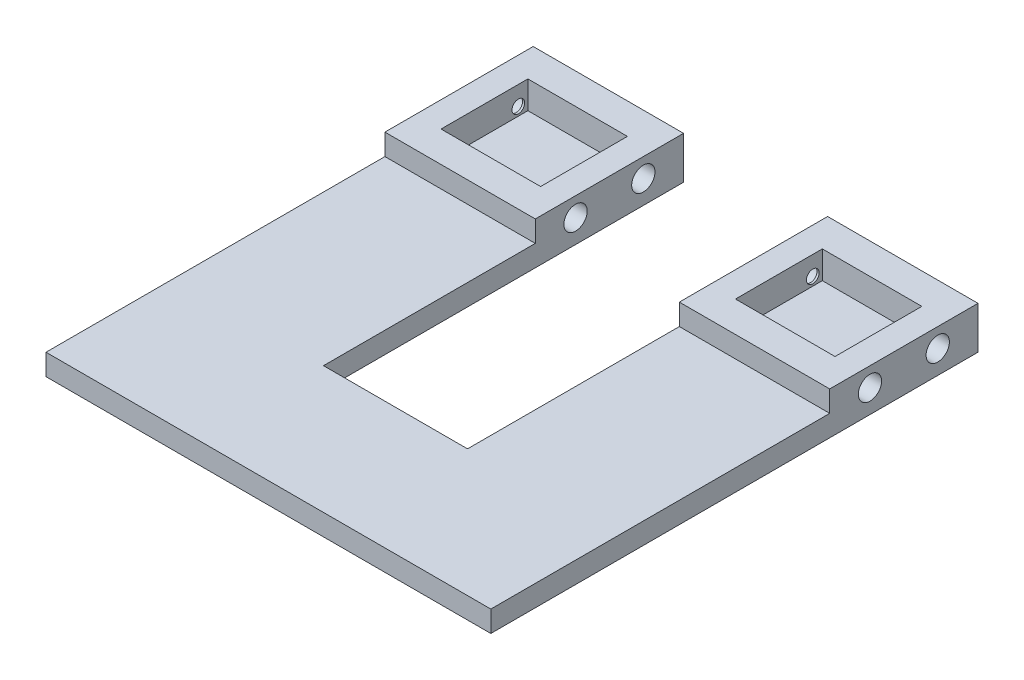
SolidWorks part; units mm, degrees
ref_plane "Front Plane" through (0, 0, 0) normal (0, 0, 1) x (1, 0, 0)
ref_plane "Top Plane" through (0, 0, 0) normal (0, 1, 0) x (1, 0, 0)
ref_plane "Right Plane" through (0, 0, 0) normal (1, 0, 0) x (0, 0, -1)
sketch "Sketch1" plane through (0, 0, 0) normal (0, 1, 0) x (1, 0, 0)
  line L1 (-11.75, 10.25) -> (11.75, 10.25)
  line L2 (-11.75, 10.25) -> (-11.75, -10.25)
  line L3 (-11.75, -10.25) -> (11.75, -10.25)
  line L4 (11.75, 10.25) -> (11.75, -10.25)
  line L5 (0, -10.25) -> (0, 10.25) construction
  line L6 (-11.75, 0) -> (11.75, 0) construction
  line L7 (-17.75, -17.5) -> (17.75, -17.5)
  line L8 (-17.75, -17.5) -> (-17.75, 17.5)
  line L9 (-17.75, 17.5) -> (17.75, 17.5)
  line L10 (17.75, -17.5) -> (17.75, 17.5)
  line L11 (0, 17.5) -> (0, -17.5) construction
  line L12 (-17.75, 0) -> (17.75, 0) construction
  point P0 (0, 0)
  point P4 (0, 0)
  dimension "D1" = 23.5
  dimension "D2" = 20.5
  dimension "D3" = 7.25
  dimension "D4" = 6
extrude "Boss-Extrude1" add sketch "Sketch1" along normal blind 10
extrude "Boss-Extrude2" add sketch "Sketch1<2>" along normal blind 3.5 contours L4 L1 L2 L3 region at (0, 0, 0)
sketch "Sketch1<2>" plane through (0, 0, 0) normal (0, 1, 0) x (1, 0, 0) same geometry as "Sketch1"
sketch "Sketch2" plane through (17.75, 0, 0) normal (1, 0, 0) x (0, 0, -1)
  line L0 (0, 0) -> (0, 50000) construction
  line L1 (8, 5.5) -> (-8, 5.5) construction
  line L2 (-17.5, 10) -> (17.5, 10) construction
  circle A0 centre (-8, 5.5) radius 2.75
  circle A1 centre (8, 5.5) radius 1.5
  circle A2 centre (-8, 5.5) radius 1.5
  circle A3 centre (8, 5.5) radius 2.75
  point P6 (0, 5.5)
  dimension "D3" = 5.5
  dimension "D4" = 3
  dimension "D5" = 3
  dimension "D6" = 5.5
  dimension "D1" = 16
  dimension "D2" = 4.5
extrude "Cut-Extrude1" cut sketch "Sketch2" against normal blind 5.5
extrude "Cut-Extrude2" cut sketch "Sketch2<2>" against normal through all contours A2 | A1 region at (17.75, 5.5, -8) region at (17.75, 5.5, 8)
sketch "Sketch2<2>" plane through (17.75, 0, 0) normal (1, 0, 0) x (0, 0, -1) same geometry as "Sketch2"
extrude "Cut-Extrude3" cut sketch "Sketch2<3>" along normal blind 5.5 from surface starting at face at (-17.75, 5.5, 6.5)
sketch "Sketch2<3>" plane through (17.75, 0, 0) normal (1, 0, 0) x (0, 0, -1) same geometry as "Sketch2"
ref_plane "Plane1" through (-34.75, 0, 0) normal (-1, 0, 0) x (0, 0, 1)
mirror "Mirror1" about plane through (-34.75, 0, 0) normal (-1, 0, 0) of bodies 105
sketch "Sketch4" plane through (0, 0, 0) normal (0, 1, 0) x (1, 0, 0)
  line L0 (-51.75, -17.5) -> (-51.75, -67.5)
  line L1 (-51.75, -67.5) -> (-17.75, -67.5)
  line L2 (-17.75, -67.5) -> (-17.75, -17.5)
  line L4 (-51.75, -17.5) -> (-87.25, -17.5)
  line L5 (-87.25, -17.5) -> (-87.25, -97.5)
  line L6 (17.75, -17.5) -> (17.75, -97.5)
  line L7 (17.75, -97.5) -> (-87.25, -97.5)
  line L8 (-17.75, -17.5) -> (17.75, -17.5)
  point P11 (0, 0)
  dimension "D1" = 50
  dimension "D2" = 34
  dimension "D3" = 80
  dimension "D4" = 80
extrude "Boss-Extrude3" add sketch "Sketch4" along normal blind 5
sketch "Sketch5" plane through (0, 0, 0) normal (0, 1, 0) x (1, 0, 0)
  line L0 (-34.75, 5.5) -> (-34.75, -5.5) construction
  circle A0 centre (-34.75, 0) radius 12.5
  circle A1 centre (-34.75, 0) radius 17.5
  dimension "D1" = 25
  dimension "D2" = 35
sketch "Sketch7" plane through (0, 0, 0) normal (0, -1, 0) x (1, 0, 0)
  line L0 (4.25, 0) -> (-73.75, 0) construction
  line L2 (-73.75, 7.5) -> (-73.75, -7.5)
  line L3 (-73.75, -7.5) -> (-48.75, -7.5)
  line L4 (-48.75, -7.5) -> (-48.75, 7.5)
  line L5 (-48.75, 7.5) -> (-73.75, 7.5)
  line L6 (-34.75, 5.5) -> (-34.75, -5.5) construction
  line L7 (-20.75, -7.5) -> (-20.75, 7.5)
  line L8 (4.25, -7.5) -> (-20.75, -7.5)
  line L9 (4.25, 7.5) -> (4.25, -7.5)
  line L10 (-20.75, 7.5) -> (4.25, 7.5)
  point P4 (-34.75, 0)
  point P8 (-73.75, 0)
  point P16 (4.25, 0)
  dimension "D1" = 7.5
  dimension "D2" = 25
